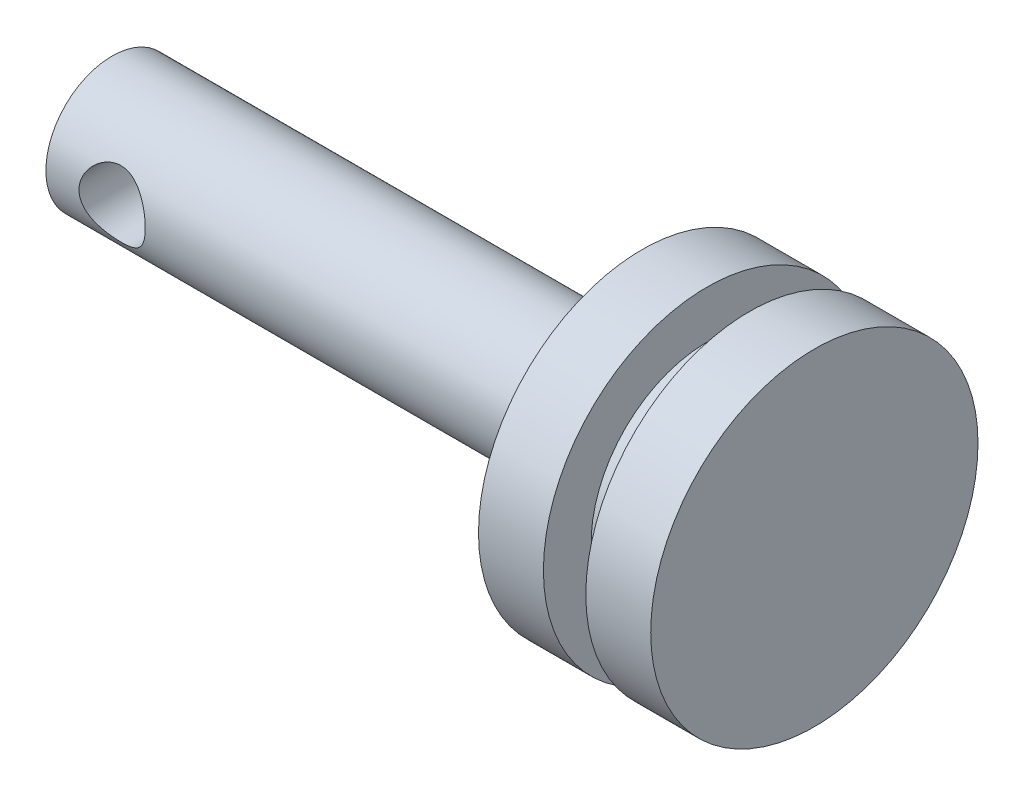
SolidWorks part; units mm, degrees
ref_plane "Front Plane" through (0, 0, 0) normal (0, 0, 1) x (1, 0, 0)
ref_plane "Top Plane" through (0, 0, 0) normal (0, 1, 0) x (1, 0, 0)
ref_plane "Right Plane" through (0, 0, 0) normal (1, 0, 0) x (0, 0, -1)
sketch "Sketch1" plane through (0, 0, 0) normal (0, 0, 1) x (1, 0, 0)
  line L0 (0, 0) -> (0, 5)
  line L1 (0, 5) -> (40, 5)
  line L2 (40, 5) -> (40, 12.35)
  line L3 (40, 12.35) -> (44.9, 12.35)
  line L4 (44.9, 12.35) -> (44.9, 8.75)
  line L5 (44.9, 8.75) -> (48.1, 8.75)
  line L6 (48.1, 8.75) -> (48.1, 12.35)
  line L7 (48.1, 12.35) -> (53, 12.35)
  line L8 (53, 12.35) -> (53, 0)
  line L9 (53, 0) -> (0, 0)
  dimension "D1" = 53
  dimension "D2" = 12.35
  dimension "D3" = 40
  dimension "D4" = 5
  dimension "D5" = 3.2
  dimension "D6" = 3.6
revolve "Revolve1" add sketch "Sketch1" angle 360 about L9
sketch "Sketch2" plane through (0, 0, 0) normal (0, 0, 1) x (1, 0, 0)
  circle A0 centre (5, 0) radius 2.5
  dimension "D1" = 5
  dimension "D2" = 5
extrude "Cut-Extrude1" cut sketch "Sketch2" against normal blind 10 and the other way blind 10
